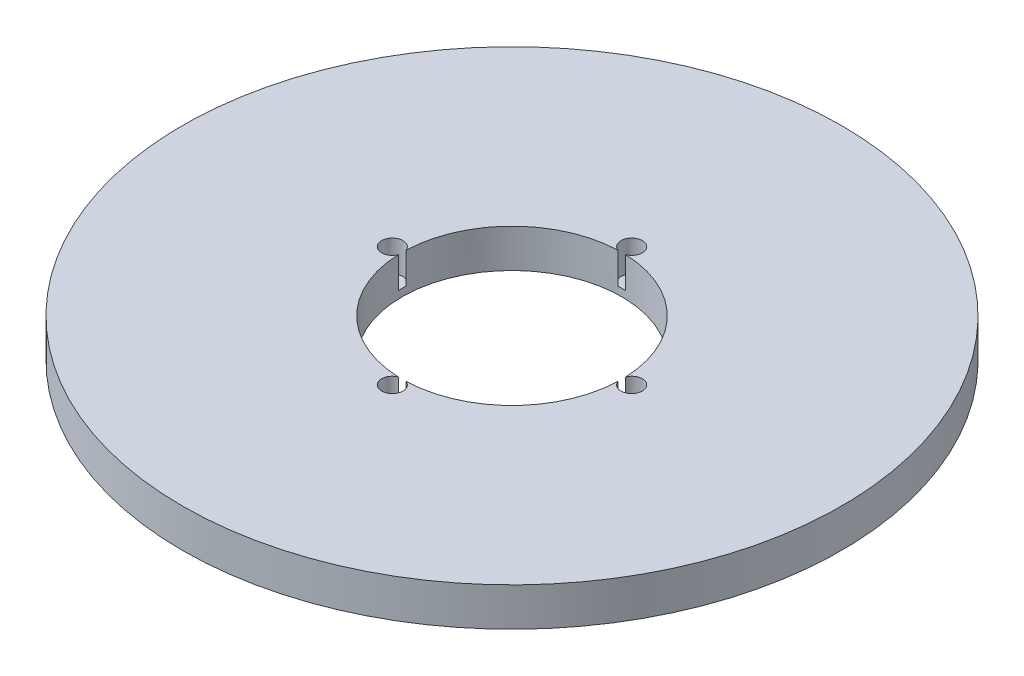
SolidWorks part; units mm, degrees
ref_plane "Front Plane" through (0, 0, 0) normal (0, 0, 1) x (1, 0, 0)
ref_plane "Top Plane" through (0, 0, 0) normal (0, 1, 0) x (1, 0, 0)
ref_plane "Right Plane" through (0, 0, 0) normal (1, 0, 0) x (0, 0, -1)
sketch "Sketch1" plane through (0, 0, 0) normal (0, 1, 0) x (1, 0, 0)
  circle A0 centre (0, 0) radius 60
  dimension "FLANGE_OD" = 120
extrude "Boss-Extrude1" add sketch "Sketch1" along normal blind 7
sketch "Sketch2" plane through (0, 0, 0) normal (0, 1, 0) x (1, 0, 0)
  circle A0 centre (0, 0) radius 20
  dimension "BORE_D" = 40
extrude "Cut-Extrude1" cut sketch "Sketch2" along normal through all
sketch "Sketch3" plane through (0, 7, 0) normal (0, 1, 0) x (1, 0, 0)
  circle A0 centre (0, 0) radius 21.7902 construction
  circle A1 centre (-21.7902, 0) radius 1.9382
  dimension "BOLT_D" = 3.8765
  dimension "BOLT_PCD" = 43.5804
extrude "Cut-Extrude2" cut sketch "Sketch3" against normal blind 5.6753
pattern_circular "CirPattern1" count 4 over 360 about axis through (0, 0, 0) along (0, 1, 0) of "Cut-Extrude2"
